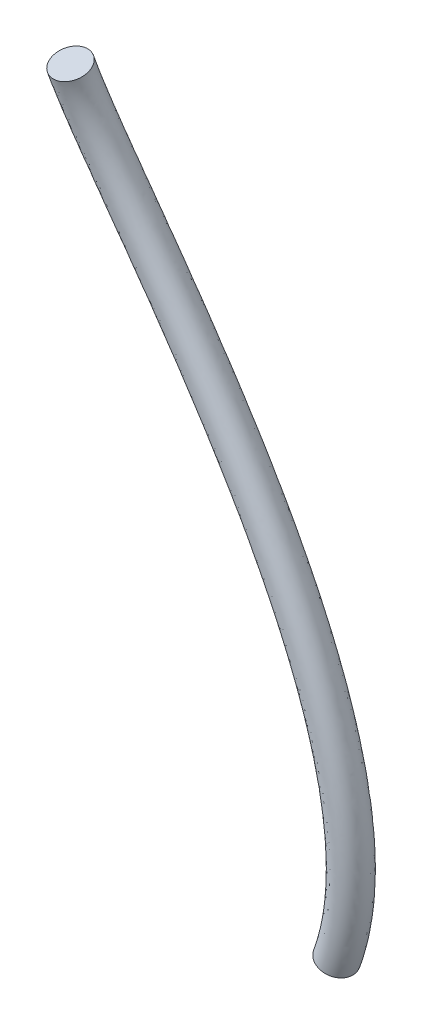
SolidWorks part; units mm, degrees
material "Custom Plastic"
ref_plane "X-Y Datum" through (0, 0, 0) normal (0, 0, 1) x (1, 0, 0)
ref_plane "X-Z Datum" through (0, 0, 0) normal (0, 1, 0) x (1, 0, 0)
ref_plane "Y-Z Datum" through (0, 0, 0) normal (1, 0, 0) x (0, 0, -1)
sketch3d "3DSketch1"
  line L0 (-113.3365, -164.006, 233.451) -> (-113.3365, -140.506, 233.451) construction
  circle A0 centre (-158.0793, -45.7731, 238.663) radius 2.286 construction
  spline S0 degree 3 poles (-158.0793, -45.7731, 238.663) (-156.2783, -71.6818, 230.7159) (-99.0736, -126.4904, 234.1377) (-114.6986, -168.3854, 233.3876) knots 0 0 0 0 1 1 1 1
  point P2 (-114.6986, -168.3854, 233.3876)
  point P10 (-158.0793, -48.0591, 238.663)
sweep "Sweep1" add path "3DSketch1" circular profile diameter 6.35 parameters "D3"=6.35
